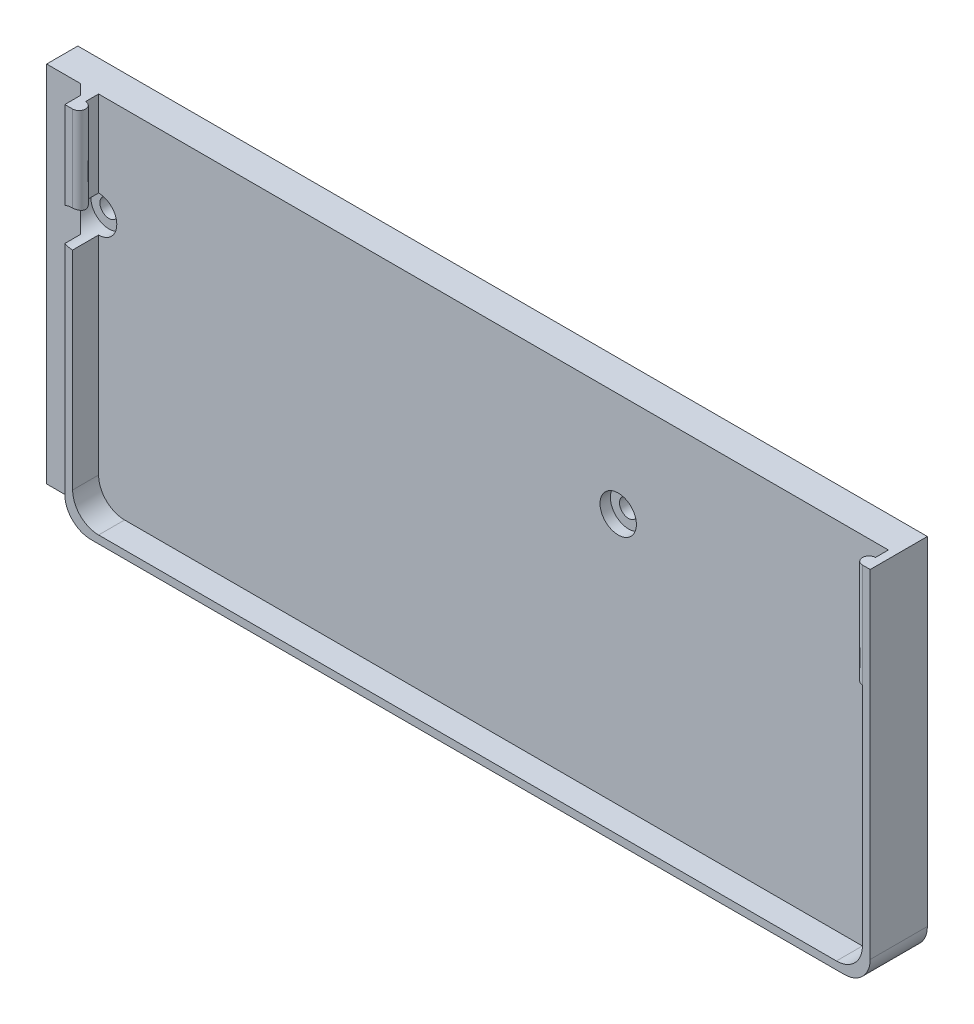
SolidWorks part; units mm, degrees
ref_plane "Piano frontale" through (0, 0, 0) normal (0, 0, 1) x (1, 0, 0)
ref_plane "Piano superiore" through (0, 0, 0) normal (0, 1, 0) x (1, 0, 0)
ref_plane "Piano destro" through (0, 0, 0) normal (1, 0, 0) x (0, 0, -1)
sketch "Schizzo1" plane through (0, 0, 0) normal (0, 0, 1) x (1, 0, 0)
  line L1 (77.5, -35) -> (-77.5, -35)
  line L2 (77.5, -35) -> (77.5, 35)
  line L3 (77.5, 35) -> (-77.5, 35)
  line L4 (-77.5, -35) -> (-77.5, 35)
  line L5 (77.5, -35) -> (-77.5, 35) construction
  line L6 (77.5, 35) -> (-77.5, -35) construction
  point P0 (0, 0)
  dimension "D1" = 155
  dimension "D2" = 70
extrude "Estrusione-Estrusione1" add sketch "Schizzo1" along normal blind 6
sketch "Schizzo3" plane through (0, 0, 6) normal (0, 0, 1) x (1, 0, 0)
  line L0 (-76, 35) -> (-76, -33.5)
  line L1 (-76, -33.5) -> (76, -33.5)
  line L2 (76, -33.5) -> (76, 35)
  line L3 (-77.5, 35) -> (-76, 35)
  line L4 (-77.5, 35) -> (-77.5, -35)
  line L5 (-77.5, -35) -> (77.5, -35)
  line L6 (77.5, -35) -> (77.5, 35)
  line L7 (77.5, 35) -> (-77.5, 35)
  line L8 (-77.5, 35) -> (-77.5, -35)
  line L9 (-77.5, -35) -> (77.5, -35)
  line L10 (77.5, -35) -> (77.5, 35)
  line L11 (77.5, 35) -> (76, 35)
  dimension "D1" = 0
  dimension "D2" = 1.5
extrude "Estrusione-Estrusione3" add sketch "Schizzo3" along normal blind 5
fillet "Raccordo1" radius 5 2 edges at (76, -33.5, 8.5) (-76, -33.5, 8.5)
sketch "Schizzo4" plane through (0, 35, 0) normal (0, 1, 0) x (1, 0, 0)
  line L0 (76, -11) -> (76, -8.5)
  line L1 (76, -11) -> (76, -6) construction
  arc A0 (76, -8.5) -> (76, -11) centre (76, -9.75) ccw
extrude "Estrusione-Estrusione4" add sketch "Schizzo4" against normal blind 20
mirror "Specchia1" about plane through (0, 0, 0) normal (1, 0, 0) of "Estrusione-Estrusione4"
fillet "Raccordo2" radius 5 2 edges at (77.5, -35, 5.5) (-77.5, -35, 5.5)
sketch "Schizzo6" plane through (0, 0, 0) normal (0, 0, 1) x (1, 0, 0)
  line L0 (-72.5, -35) -> (72.5, -35) construction
  line L1 (77.5, 35) -> (-86, 35)
  line L2 (77.5, 35) -> (77.5, -35)
  line L3 (77.5, -35) -> (-86, -35)
  line L4 (-86, 35) -> (-86, -35)
  line L5 (-76, -28.5) -> (-76, 35) construction
  line L15 (-72.5, -35) -> (72.5, -35)
  line L16 (77.5, -30) -> (77.5, 35)
  line L17 (77.5, 35) -> (76, 35)
  line L18 (76, 35) -> (76, 15)
  line L19 (76, 15) -> (76, -28.5)
  line L20 (71, -33.5) -> (-71, -33.5)
  line L21 (-76, -28.5) -> (-76, 15)
  line L22 (-76, 35) -> (-77.5, 35)
  line L23 (-77.5, 35) -> (-77.5, -30)
  line L24 (-72.5, -35) -> (72.5, -35)
  line L25 (77.5, -30) -> (77.5, 35)
  line L26 (77.5, 35) -> (76, 35)
  line L27 (76, 35) -> (76, 15)
  line L28 (76, 15) -> (76, -28.5)
  line L29 (71, -33.5) -> (-71, -33.5)
  line L30 (-76, -28.5) -> (-76, 15)
  line L31 (-76, 35) -> (-77.5, 35)
  line L32 (-77.5, 35) -> (-77.5, -30)
  line L34 (-76, 15) -> (-76, 35)
  line L35 (-76, 15) -> (-76, 35)
  arc A4 (72.5, -35) -> (77.5, -30) centre (72.5, -30) ccw
  arc A5 (71, -33.5) -> (76, -28.5) centre (71, -28.5) ccw
  arc A6 (-76, -28.5) -> (-71, -33.5) centre (-71, -28.5) ccw
  arc A7 (-77.5, -30) -> (-72.5, -35) centre (-72.5, -30) ccw
  arc A8 (72.5, -35) -> (77.5, -30) centre (72.5, -30) ccw
  arc A9 (71, -33.5) -> (76, -28.5) centre (71, -28.5) ccw
  arc A10 (-76, -28.5) -> (-71, -33.5) centre (-71, -28.5) ccw
  arc A11 (-77.5, -30) -> (-72.5, -35) centre (-72.5, -30) ccw
  point P7 (-4.25, -35)
  dimension "D1" = 10
  dimension "D2" = 0
extrude "Estrusione-Estrusione5" add sketch "Schizzo6" along normal up to surface (6 mm away) contours A11 L32 L1 L4 L3 up to face at (0, -9.3452, 6)
sketch "Schizzo7" plane through (0, 0, 0) normal (0, 0, -1) x (-1, 0, 0)
  line L0 (-24, 15) -> (76, 15) construction
  line L1 (86, 35) -> (86, -35) construction
  line L2 (86, -35) -> (-72.5, -35) construction
  circle A0 centre (-24, 15) radius 1.75
  circle A1 centre (76, 15) radius 1.75
  dimension "D4" = 3.5
  dimension "D1" = 100
  dimension "D2" = 10
  dimension "D3" = 50
extrude "Taglio-Estrusione2" cut sketch "Schizzo7" against normal through all
hole_wizard "Foro1" positions "Schizzo3D1" profile "Schizzo8" legacy
sketch3d "Schizzo3D1"
  line L0 (24, 15, 6) -> (24, 15, 0) construction
  line L1 (-76, 15, 6) -> (-76, 15, 0) construction
  point P0 (24, 15, 6)
  point P4 (-76, 15, 6)
sketch "Schizzo8" plane through (24, 15, 6) normal (1, 0, 0) x (0, -1, 0)
  line L0 (0, 0) -> (0, 7.0515)
  line L1 (0, 7.0515) -> (1.75, 6)
  line L2 (1.75, 6) -> (1.75, 2)
  line L3 (1.75, 2) -> (3.5, 2)
  line L4 (3.5, 0) -> (0, 0)
  line L5 (0, -11.3109) -> (0, 121.1557) construction
  line L6 (0, 7.0515) -> (-1.75, 6) construction
  line L7 (3.5, 2) -> (3.5, 0)
  dimension "Depth" = 6
  dimension "Drill Angle" = 118
  dimension "Diameter" = 3.5
  dimension "C-Bore Diameter" = 7
  dimension "C-Bore Depth" = 2
sketch "Schizzo9" plane through (0, 0, 4) normal (0, 0, 1) x (1, 0, 0)
  circle A1 centre (-76, 15) radius 3.5
  circle A2 centre (-76, 15) radius 3.5
  dimension "D1" = 0
extrude "Taglio-Estrusione3" cut sketch "Schizzo9" along normal through all
chamfer "Smusso1" distance 2 angle 45 2 edges at (-76.0355, -33.5355, 6) (-77.5, 26.5811, 6)
